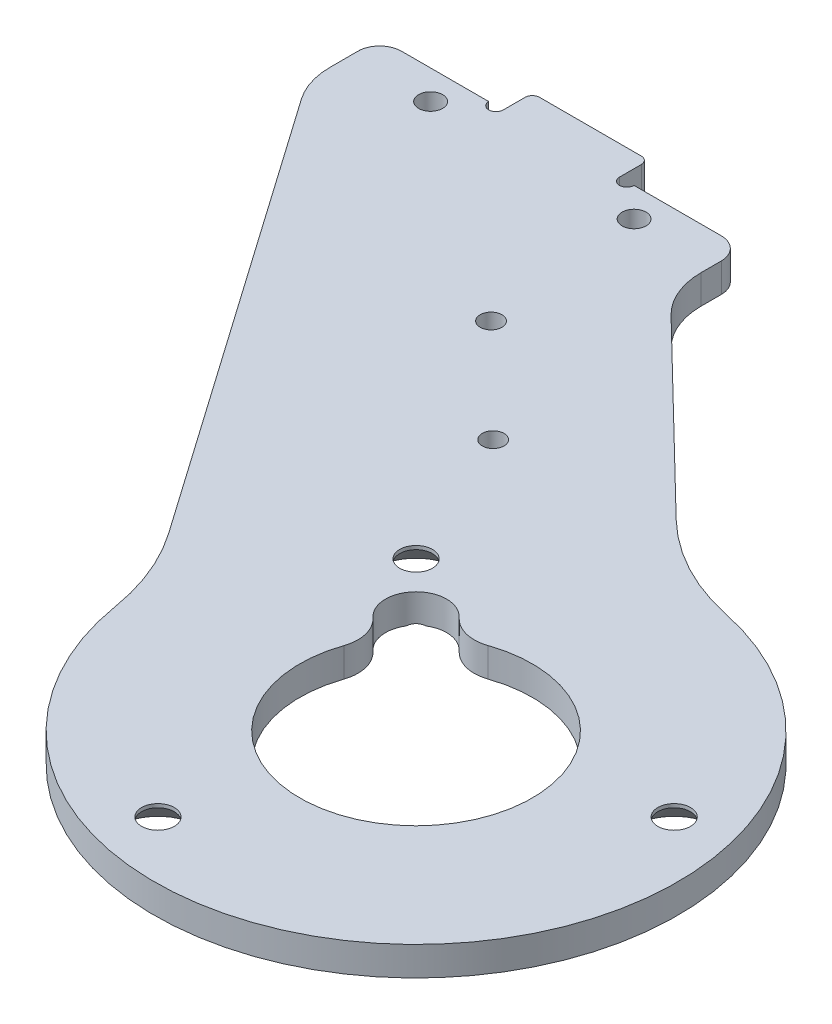
SolidWorks part; units mm, degrees
material "Thornel Mat VMA"
ref_plane "前视基准面" through (0, 0, 0) normal (0, 0, 1) x (1, 0, 0)
ref_plane "上视基准面" through (0, 0, 0) normal (0, 1, 0) x (1, 0, 0)
ref_plane "右视基准面" through (0, 0, 0) normal (1, 0, 0) x (0, 0, -1)
sketch "草图1" plane through (0, 0, 0) normal (0, 1, 0) x (1, 0, 0)
  line L0 (-46.0918, 2.5735) -> (107.1195, 22.8576) construction
  line L1 (-85, 80) -> (-35, 80)
  line L2 (101.4093, -246.5221) -> (869.4093, -246.5221) construction
  line L3 (-35, 80) -> (-35, 70)
  line L4 (-85, 80) -> (-85, 70)
  line L5 (-85, 70) -> (-36, 0)
  line L6 (0, 0) -> (-109.1595, 0) construction
  line L7 (0, 0) -> (0, 75.0483) construction
  line L8 (0, 0) -> (81.4628, 0) construction
  line L9 (0, 0) -> (0, -69.3688) construction
  line L10 (0, 36) -> (-35, 70)
  line L11 (-60, 80) -> (-60, -8.6185) construction
  arc A0 (-36, 0) -> (0, 36) centre (0, 0) ccw
  circle A1 centre (0, 0) radius 36 construction
  arc A2 (0, 36) -> (-36, 0) centre (0, 0) ccw construction
  circle A3 centre (0, 0) radius 36 construction
  dimension "D6" = 36
  dimension "D1" = 50
  dimension "D2" = 60
  dimension "D3" = 10
  dimension "D4" = 10
  dimension "D5" = 80
extrude "凸台-拉伸1" add sketch "草图1" along normal blind 4
fillet "圆角1" radius 30 1 edges at (0, 2, -36)
fillet "圆角2" radius 30 1 edges at (-36, 2, 0)
sketch "草图2" plane through (0, 4, 0) normal (0, 1, 0) x (1, 0, 0)
  line L0 (0, 0) -> (-20.5061, 20.5061) construction
  line L1 (-29, 0) -> (29, 0) construction
  line L2 (0, 29) -> (0, -29) construction
  circle A0 centre (0, 0) radius 29 construction
  circle A1 centre (-20.5061, 20.5061) radius 2.25
  circle A2 centre (28.0118, 7.5058) radius 2.25
  circle A3 centre (-7.5058, -28.0118) radius 2.25
  circle A4 centre (0, 0) radius 16
  dimension "D1" = 58
  dimension "D3" = 4.5
  dimension "D5" = 32
  dimension "D2" = 45
  dimension "D4" = 3
extrude "切除-拉伸1" cut sketch "草图2" against normal blind 4
sketch "草图3" plane through (0, 4, 0) normal (0, 1, 0) x (1, 0, 0)
  line L0 (-20.5061, 20.5061) -> (0, 0) construction
  circle A0 centre (-13.6118, 13.6118) radius 4.2
  dimension "D2" = 8.4
  dimension "D1" = 19.25
extrude "切除-拉伸2" cut sketch "草图3" against normal blind 4
fillet "圆角3" radius 5 2 edges at (-9.4736, 2, -12.8938) (-12.8938, 2, -9.4736)
sketch "草图4" plane through (0, 4, 0) normal (0, 1, 0) x (1, 0, 0)
  line L0 (-60, 80) -> (-60, 15.697) construction
  line L1 (-35, 80) -> (-85, 80) construction
  circle A0 centre (-46, 76) radius 1.65
  circle A1 centre (-74, 76) radius 1.65
  dimension "D1" = 28
  dimension "D2" = 3.3
  dimension "D3" = 4
extrude "切除-拉伸3" cut sketch "草图4" against normal blind 4
fillet "圆角4" radius 10 2 edges at (-85, 2, -70) (-35, 2, -70)
fillet "圆角5" radius 3 2 edges at (-85, 2, -80) (-35, 2, -80)
sketch "草图7" plane through (0, 4, 0) normal (0, 1, 0) x (1, 0, 0)
  line L0 (-60, 80) -> (-60, 94.9774) construction
  line L1 (-38, 80) -> (-82, 80) construction
  line L3 (-68, 84) -> (-52, 84)
  line L4 (-68, 84) -> (-68, 80)
  line L5 (-68, 80) -> (-52, 80)
  line L6 (-52, 84) -> (-52, 80)
  line L7 (-60, 80) -> (-60, 84) construction
  line L8 (-68, 82) -> (-52, 82) construction
  point P4 (-60, 82)
  dimension "D1" = 4
  dimension "D2" = 16
extrude "凸台-拉伸3" add sketch "草图7" against normal blind 4
sketch "草图8" plane through (0, 4, 0) normal (0, 1, 0) x (1, 0, 0)
  line L1 (-50, 80) -> (-52, 80)
  line L2 (-60, 84) -> (-60, 22.1698) construction
  line L3 (-52, 84) -> (-68, 84) construction
  line L4 (-70, 80) -> (-68, 80)
  arc A1 (-52, 80) -> (-50, 80) centre (-51, 80) ccw
  arc A2 (-68, 80) -> (-70, 80) centre (-69, 80) cw
  dimension "D1" = 1
extrude "切除-拉伸5" cut sketch "草图8" against normal blind 4
fillet "圆角7" radius 1 2 edges at (-68, 2, -84) (-52, 2, -84)
chamfer "倒角1" distance 3.5 angle 45 3 edges at (28.0118, 0, -5.2558) (-7.5058, 0, 30.2618) (-20.5061, 0, -18.2561)
sketch "草图9" plane through (0, 0, 0) normal (0, -1, 0) x (1, 0, 0)
  circle A0 centre (-29.4012, -40.0071) radius 1.2 construction
  circle A1 centre (-43.6869, -54.0042) radius 1.2 construction
  circle A2 centre (-29.4012, -40.0071) radius 1.2
  circle A3 centre (-43.6869, -54.0042) radius 1.2
extrude "切除-拉伸6" cut sketch "草图9" against normal blind 10
sketch "草图10" plane through (0, 0, 0) normal (0, -1, 0) x (1, 0, 0)
  circle A0 centre (-29.4012, -40.0071) radius 1.5
  circle A1 centre (-43.6869, -54.0042) radius 1.5
  dimension "D1" = 3
  dimension "D2" = 3
extrude "切除-拉伸7" cut sketch "草图10" against normal blind 10
